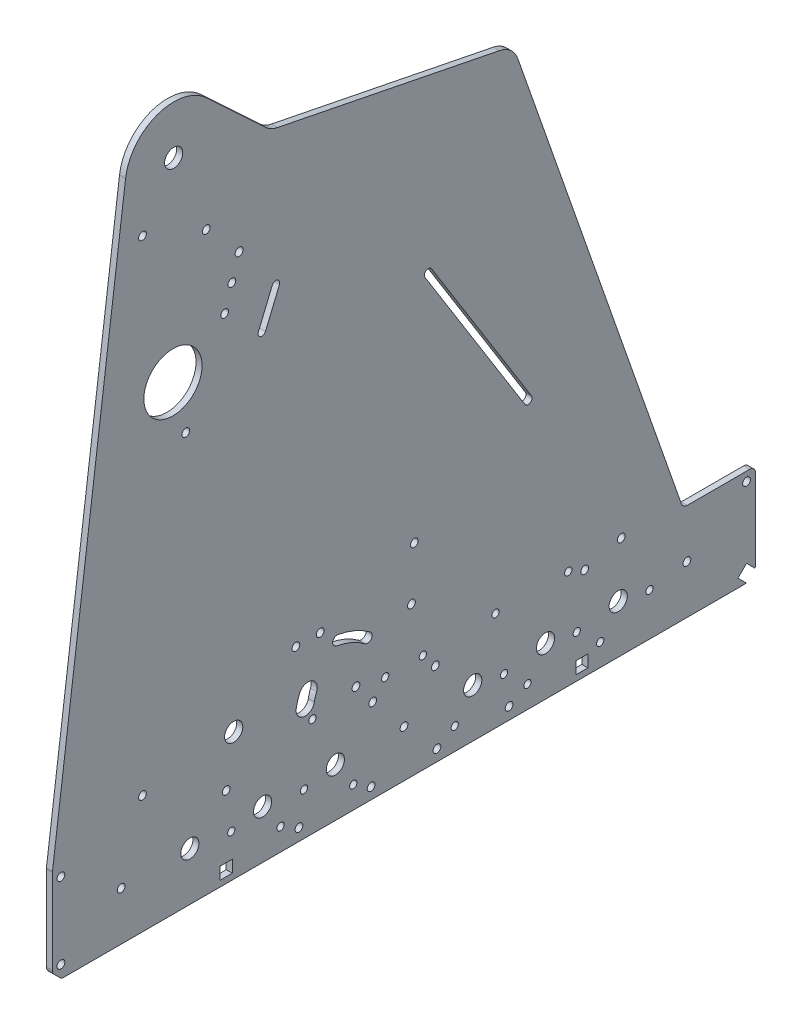
SolidWorks part; units mm, degrees
ref_plane "Front Plane" through (0, 0, 0) normal (0, 0, 1) x (1, 0, 0)
ref_plane "Top Plane" through (0, 0, 0) normal (0, 1, 0) x (1, 0, 0)
ref_plane "Right Plane" through (0, 0, 0) normal (1, 0, 0) x (0, 0, -1)
sketch "Sketch1" plane through (0, 0, 0) normal (1, 0, 0) x (0, 0, -1)
  line L0 (-184.15, -24.6062) -> (184.15, -24.6062)
  line L1 (184.15, -24.6062) -> (184.15, 26.1938)
  line L2 (184.15, 26.1938) -> (146.05, 26.1937)
  line L3 (146.05, 26.1937) -> (57.15, 280.1938)
  line L5 (-145.839, 321.5609) -> (-184.15, 26.1938)
  line L6 (-184.15, 26.1938) -> (-184.15, -24.6062)
  line L7 (-184.15, 350.0437) -> (184.15, 350.0437) construction
  line L8 (57.15, 280.1938) -> (-69.85, 305.5938)
  line L9 (-69.85, 305.5938) -> (-103.3099, 336.854)
  arc A0 (-103.3099, 336.854) -> (-145.839, 321.5609) centre (-120.65, 318.2937) ccw
  point P8 (0, -24.6062)
  dimension "D1" = 368.3
  dimension "D7" = 25.4
  dimension "D2" = 50.8
  dimension "D3" = 38.1
  dimension "D4" = 24.6062
  dimension "D5" = 374.65
  dimension "D6" = 304.8
  dimension "D8" = 342.9
  dimension "D9" = 127
  dimension "D10" = 304.8
  dimension "D11" = 25.4
  dimension "D12" = 127
extrude "Boss-Extrude1" add sketch "Sketch1" along normal blind 3.175
chamfer "Chamfer1" distance 4.7625 angle 45 2 edges at (1.5875, -24.6062, 184.15) (1.5875, -24.6062, -184.15)
fillet "Fillet1" radius 12.7 2 edges at (1.5875, 305.5938, 69.85) (1.5875, 280.1938, -57.15)
fillet "Fillet2" radius 3.175 3 edges at (1.5875, 26.1938, 184.15) (1.5875, 26.1938, -184.15) (1.5875, 26.1937, -146.05)
fillet "Fillet3" radius 3.175 4 edges at (1.5875, -19.8438, -184.15) (1.5875, -24.6062, -179.3875) (1.5875, -19.8437, 184.15) (1.5875, -24.6062, 179.3875)
sketch "Sketch30" plane through (3.175, 0, 0) normal (1, 0, 0) x (0, 0, -1)
  circle A8 centre (-89.211, 42.2593) radius 4.7625
  circle A9 centre (-25.1593, 30.6938) radius 2.032
  arc A10 (-51.7173, 35.4892) -> (-50.2741, 40.5715) centre (-25.1593, 30.6938) cw construction
  arc A11 (-54.7652, 42.3379) -> (-56.4665, 36.3468) centre (-25.1593, 30.6938) ccw
  arc A12 (-45.783, 38.8051) -> (-46.9681, 34.6317) centre (-25.1593, 30.6938) ccw
  arc A13 (-45.783, 38.8051) -> (-54.7652, 42.3379) centre (-50.2741, 40.5715) ccw
  arc A14 (-56.4665, 36.3468) -> (-46.9681, 34.6317) centre (-51.7173, 35.4892) ccw
  arc A15 (-34.9881, 56.6661) -> (-19.1131, 49.8125) centre (-41.7582, 19.1724) cw construction
  arc A16 (-17.6789, 51.753) -> (-34.5594, 59.0407) centre (-41.7582, 19.1724) ccw
  arc A17 (-20.5473, 47.8719) -> (-35.4169, 54.2915) centre (-41.7582, 19.1724) ccw
  arc A18 (-20.5473, 47.8719) -> (-17.6789, 51.753) centre (-19.1131, 49.8125) ccw
  arc A19 (-34.5594, 59.0407) -> (-35.4169, 54.2915) centre (-34.9881, 56.6661) ccw
  arc A20 (-19.1131, 49.8125) -> (-34.9881, 56.6661) centre (-41.7582, 19.1724) ccw construction
  circle A21 centre (94.6345, 23.8125) radius 2.032
  circle A22 centre (-56.6241, 64.5541) radius 2.032
  circle A23 centre (-43.9241, 64.5541) radius 2.032
  circle A24 centre (-56.6241, 64.5541) radius 1.905 construction
  circle A25 centre (-43.9241, 64.5541) radius 1.905 construction
  point P7 (-51.1204, 38.0658)
  point P19 (-26.6567, 54.1518)
  dimension "D2" = 9.652
  dimension "D4" = 4.064
  dimension "D1" = 4.064
  dimension ".375" = 9.525
  dimension "D3" = 4.826
extrude "Cut-Extrude9" cut sketch "Sketch30" against normal through all
sketch "Sketch16" plane through (3.175, 0, 0) normal (1, 0, 0) x (0, 0, -1)
  circle A0 centre (112.1746, 0.7937) radius 4.7625
  circle A1 centre (74.0746, 0.7937) radius 4.7625
  circle A2 centre (35.9746, 0.7937) radius 4.7625
  circle A3 centre (-35.9746, 0.7938) radius 4.7625
  circle A4 centre (-74.0746, 0.7938) radius 4.7625
  circle A5 centre (-112.1746, 0.7937) radius 4.7625
  dimension "D1" = 9.525
  dimension "D2" = 9.525
extrude "Cut-Extrude1" cut sketch "Sketch16" against normal up to next
sketch "Sketch25" plane through (3.175, 0, 0) normal (1, 0, 0) x (0, 0, -1)
  circle A0 centre (102.7672, -13.0003) radius 1.905 construction
  circle A1 centre (86.0486, 27.3622) radius 1.905 construction
  circle A2 centre (128.5804, -2.3081) radius 1.905 construction
  circle A3 centre (102.7672, -13.0003) radius 1.905
  circle A4 centre (86.0486, 27.3622) radius 1.905
  circle A5 centre (128.5804, -2.3081) radius 1.905
  circle A6 centre (64.6672, -13.0003) radius 1.905 construction
  circle A8 centre (-9.8486, 27.3622) radius 1.905 construction
  circle A10 centre (-47.9486, 27.3622) radius 1.905 construction
  circle A11 centre (-90.4804, -2.3081) radius 1.905 construction
  circle A12 centre (-64.6672, -13.0003) radius 1.905 construction
  circle A14 centre (-52.3804, -2.3081) radius 1.905 construction
  circle A15 centre (-26.5672, -13.0003) radius 1.905 construction
  circle A16 centre (9.8486, 27.3622) radius 1.905 construction
  circle A17 centre (26.5672, -13.0003) radius 1.905 construction
  circle A18 centre (47.9486, 27.3622) radius 1.905 construction
  circle A19 centre (52.3804, -2.3081) radius 1.905 construction
  circle A20 centre (90.4804, -2.3081) radius 1.905 construction
  circle A21 centre (-9.8486, 27.3622) radius 1.905
  circle A23 centre (-47.9486, 27.3622) radius 1.905
  circle A24 centre (-90.4804, -2.3081) radius 1.905
  circle A25 centre (-64.6672, -13.0003) radius 1.905
  circle A27 centre (-52.3804, -2.3081) radius 1.905
  circle A28 centre (-26.5672, -13.0003) radius 1.905
  circle A29 centre (9.8486, 27.3622) radius 1.905
  circle A30 centre (26.5672, -13.0003) radius 1.905
  circle A31 centre (47.9486, 27.3622) radius 1.905
  circle A32 centre (64.6672, -13.0003) radius 1.905
  circle A33 centre (52.3804, -2.3081) radius 1.905
  circle A34 centre (90.4804, -2.3081) radius 1.905
extrude "Cut-Extrude4" cut sketch "Sketch25" against normal up to next
sketch "Sketch23" plane through (3.175, 0, 0) normal (1, 0, 0) x (0, 0, -1)
  point P0 (-55.0246, -18.3223)
  point P6 (-93.1246, 17.5943)
  point P9 (-17.2515, -18.6426)
  point P12 (-16.4124, 19.3854)
  point P15 (16.4124, 19.3854)
  point P18 (17.2515, -18.6426)
  point P21 (55.0246, -18.3223)
  point P35 (3.8736, 53.6853)
  point P38 (113.7728, 28.6594)
  point P41 (-137.0088, 37.226)
  point P44 (-179.705, 21.7487)
  point P47 (-179.705, -18.0026)
  point P50 (179.3875, 21.4312)
hole_wizard "#8 (0.16) Diameter Hole1" positions "Sketch23" profile "Sketch24" hole size "#8" standard "ANSI Inch" end condition up to next
sketch "Sketch24" plane through (3.175, -18.3223, 55.0246) normal (0, 1, 0) x (0, 0, -1)
  line L0 (0, 0) -> (0, 3.175)
  line L1 (0, 3.175) -> (2.032, 3.175)
  line L2 (2.032, 3.175) -> (2.032, 0)
  line L5 (2.032, 0) -> (0, 0)
  line L11 (0, -6.35) -> (0, 107.95) construction
  dimension "Thru Hole Dia." = 4.064
  dimension "Thru Hole Depth" = 3.175
sketch "Sketch22" plane through (3.175, 0, 0) normal (1, 0, 0) x (0, 0, -1)
  line L0 (-96.2996, -15.1473) -> (-89.9496, -15.1473) construction
  line L1 (-96.2996, -15.1473) -> (-89.9496, -15.1473)
  line L2 (-96.2996, -15.1473) -> (-96.2996, -21.4973)
  line L3 (-96.2996, -21.4973) -> (-89.9496, -21.4973)
  line L4 (-89.9496, -15.1473) -> (-89.9496, -21.4973)
  line L5 (-96.2996, -15.1473) -> (-89.9496, -21.4973) construction
  line L6 (-96.2996, -21.4973) -> (-89.9496, -15.1473) construction
  line L7 (-89.9496, -15.1473) -> (-89.9496, -19.8734) construction
  line L77 (179.3875, -24.6062) -> (183.8776, -20.1161)
  line L78 (179.3875, -24.6062) -> (174.8974, -20.1161)
  line L79 (183.8776, -20.1161) -> (179.3875, -15.626)
  line L80 (174.8974, -20.1161) -> (179.3875, -15.626)
  line L81 (180.3174, -23.6763) -> (183.2201, -20.7737) construction
  line L82 (-178.0724, -24.6062) -> (178.0724, -24.6062) construction
  line L84 (89.9496, -21.4973) -> (96.2996, -21.4973)
  line L85 (89.9496, -21.4973) -> (89.9496, -15.1473)
  line L86 (89.9496, -15.1473) -> (96.2996, -15.1473)
  line L87 (96.2996, -21.4973) -> (96.2996, -15.1473)
  line L88 (89.9496, -21.4973) -> (96.2996, -15.1473) construction
  line L89 (89.9496, -15.1473) -> (96.2996, -21.4973) construction
  point P0 (-93.1246, -18.3223)
  point P19 (93.1246, -18.3223)
  dimension "D1" = 6.35
  dimension "D2" = 6.35
extrude "Cut-Extrude3" cut sketch "Sketch22" against normal up to next
sketch "Sketch21" plane through (3.175, 0, 0) normal (1, 0, 0) x (0, 0, -1)
  circle A0 centre (-148.1579, 0.7937) radius 2.032
  circle A2 centre (0, 0) radius 2.032
  circle A3 centre (148.1579, 0.7938) radius 2.032
  dimension "D1" = 4.064
extrude "Cut-Extrude2" cut sketch "Sketch21" against normal up to next
sketch "Sketch26" plane through (3.175, 0, 0) normal (1, 0, 0) x (0, 0, -1)
  line L0 (-145.839, 321.5609) -> (-184.1236, 26.3971) construction
  line L1 (-178.0724, -24.6062) -> (178.0724, -24.6062) construction
  circle A0 centre (-121.0218, 216.6937) radius 15.24
  dimension "D1" = 30.48
  dimension "D2" = 38.1
  dimension "D3" = 241.3
extrude "Cut-Extrude5" cut sketch "Sketch26" against normal through all
sketch "Sketch27" plane through (3.175, 0, 0) normal (1, 0, 0) x (0, 0, -1)
  circle A0 centre (-120.65, 318.2937) radius 4.7625
  dimension "D1" = 9.525
extrude "Cut-Extrude6" cut sketch "Sketch27" against normal through all
sketch "Sketch28" plane through (3.175, 0, 0) normal (1, 0, 0) x (0, 0, -1)
  line L0 (-120.65, 318.2937) -> (-103.5612, 277.2599) construction
  line L1 (-103.5612, 277.2599) -> (-86.3654, 258.566) construction
  line L2 (-86.3654, 258.566) -> (-90.1612, 246.4465) construction
  line L3 (-90.1612, 246.4465) -> (-93.9569, 234.327) construction
  line L4 (-145.839, 321.5609) -> (-184.1236, 26.3971) construction
  circle A0 centre (-93.9569, 234.327) radius 2.032
  circle A1 centre (-90.1612, 246.4465) radius 2.032
  circle A2 centre (-86.3654, 258.566) radius 2.0955
  circle A3 centre (-103.5612, 277.2599) radius 2.032
  dimension "D4" = 4.064
  dimension "D5" = 4.191
  dimension "D6" = 4.064
  dimension "D1" = 25.4
  dimension "D2" = 44.45
  dimension "D3" = 12.7
  dimension "D7" = 30
  dimension "D8" = 120
  dimension "D9" = 160
extrude "Cut-Extrude7" cut sketch "Sketch28" against normal through all
sketch "Sketch29" plane through (3.175, 0, 0) normal (1, 0, 0) x (0, 0, -1)
  line L0 (-145.839, 321.5609) -> (-184.1236, 26.3971) construction
  line L1 (-67.1375, 233.9197) -> (-74.4276, 216.3198) construction
  line L2 (-65.2602, 233.1421) -> (-72.5503, 215.5422)
  line L3 (-69.0148, 234.6973) -> (-76.305, 217.0974)
  line L4 (-67.1375, 233.9197) -> (-67.1375, 253.7354) construction
  circle A0 centre (-136.9875, 291.0697) radius 2.032
  circle A2 centre (-120.65, 318.2937) radius 4.7625 construction
  arc A4 (-65.2602, 233.1421) -> (-69.0148, 234.6973) centre (-67.1375, 233.9197) ccw
  arc A5 (-76.305, 217.0974) -> (-72.5503, 215.5422) centre (-74.4276, 216.3198) ccw
  point P8 (-70.7826, 225.1198)
  dimension "D1" = 31.75
  dimension "D2" = 4.064
  dimension "D3" = 69.85
  dimension "D4" = 12.7
  dimension "D5" = 57.15
  dimension "D6" = 19.05
  dimension "D7" = 22.5
extrude "Cut-Extrude8" cut sketch "Sketch29" against normal through all
sketch "Sketch31" plane through (0, 0, 0) normal (-1, 0, 0) x (0, 0, 1)
  circle A1 centre (114.3, 190.5) radius 2.032
  dimension "D1" = 114.3
  dimension "D6" = 4.064
  dimension "D2" = 190.5
extrude "Cut-Extrude10" cut sketch "Sketch31" against normal through all
sketch "Sketch34" plane through (0, 0, 0) normal (-1, 0, 0) x (0, 0, 1)
  line L0 (-65.024, 115.57) -> (-12.7, 199.39) construction
  line L1 (-66.7477, 116.646) -> (-14.4237, 200.466)
  line L2 (-63.3003, 114.494) -> (-10.9763, 198.314)
  arc A0 (-66.7477, 116.646) -> (-63.3003, 114.494) centre (-65.024, 115.57) ccw
  arc A1 (-10.9763, 198.314) -> (-14.4237, 200.466) centre (-12.7, 199.39) ccw
  point P3 (-38.862, 157.48)
  dimension "D5" = 2.032
  dimension "D1" = 115.57
  dimension "D2" = 65.024
  dimension "D3" = 199.39
  dimension "D4" = 12.7
extrude "Cut-Extrude12" cut sketch "Sketch34" against normal through all
sketch "Sketch37" plane through (3.175, 0, 0) normal (1, 0, 0) x (0, 0, -1)
  circle A0 centre (5.3975, 80.645) radius 2.032
  circle A8 centre (0, 0) radius 2.032 construction
  dimension "D1" = 4.064
  dimension "D2" = 5.3975
  dimension "D3" = 80.645
extrude "Cut-Extrude13" cut sketch "Sketch37" against normal through all
